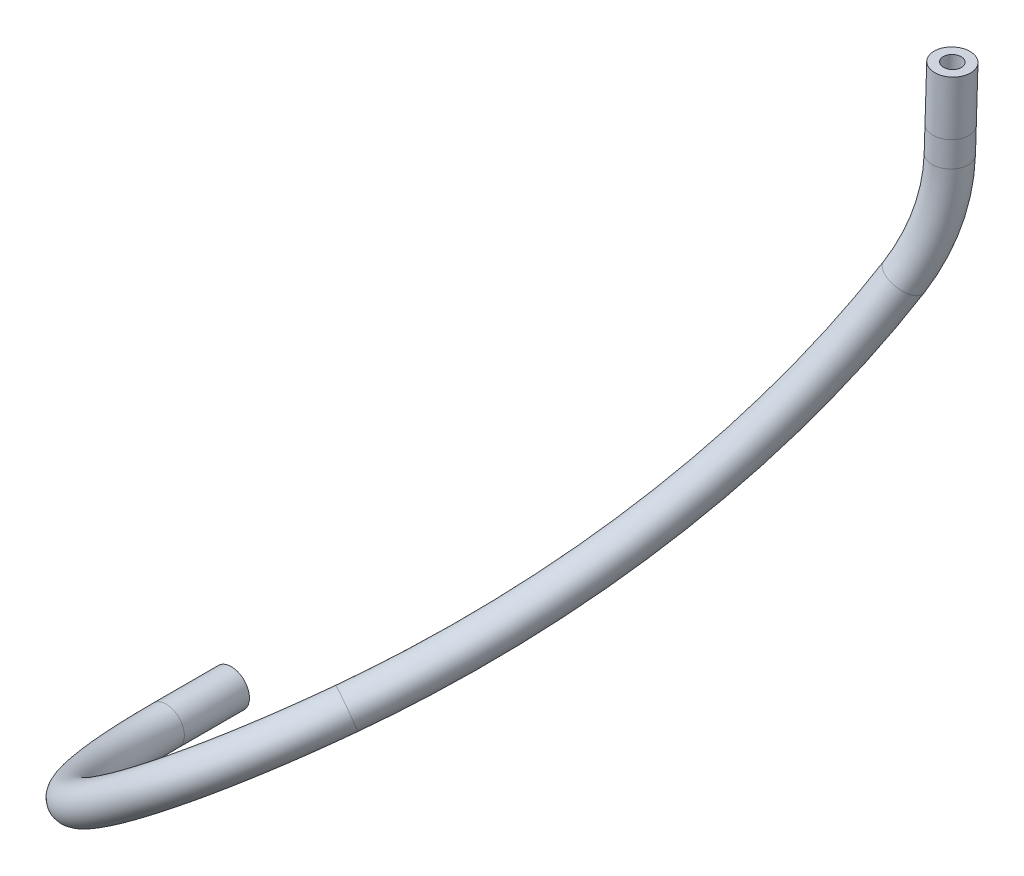
SolidWorks part; units mm, degrees
material "Silicon Rubber"
ref_plane "X-Y Datum" through (0, 0, 0) normal (0, 0, 1) x (1, 0, 0)
ref_plane "X-Z Datum" through (0, 0, 0) normal (0, 1, 0) x (1, 0, 0)
ref_plane "Y-Z Datum" through (0, 0, 0) normal (1, 0, 0) x (0, 0, -1)
sketch3d "3DSketch1"
  line L0 (44.0922, 18.6668, 9.7727) -> (44.0922, 18.6668, -12.9773)
  line L1 (44.0922, 18.6668, -12.9773) -> (44.0922, 18.6668, 9.7727) construction
  line L2 (233.3478, 252.6392, -75.3796) -> (233.125, 243.669, -75.3201)
  line L3 (233.8233, 271.7865, -75.5066) -> (233.3478, 252.6392, -75.3796)
  circle A0 centre (44.0922, 18.6668, 9.7727) radius 3.2466 construction
  circle A1 centre (233.8233, 271.7865, -75.5066) radius 9.525 construction
  arc A2 (44.0922, 18.6668, 9.7727) -> (145.7778, 93.8476, 48.368) centre (99.6708, 59.7586, 9.7727) ccw
  circle A3 centre (233.125, 243.669, -75.3201) radius 6.35 construction
  circle A4 centre (44.0922, 18.6668, 9.7727) radius 3.2466 construction
  arc A6 (40.1426, 18.718, -12.9773) -> (44.041, 14.7171, -12.9773) centre (44.0922, 18.6668, -12.9773) ccw construction
  arc A7 (233.125, 243.669, -75.3201) -> (224.9145, 206.1842, -67.4223) centre (183.0364, 245.2622, -22.6572) ccw
  arc A9 (44.041, 14.7171, -12.9773) -> (48.0419, 18.6156, -12.9773) centre (44.0922, 18.6668, -12.9773) ccw construction
  arc A10 (40.1426, 18.718, -12.9773) -> (44.041, 14.7171, -12.9773) centre (44.0922, 18.6668, -12.9773) ccw construction
  arc A11 (44.041, 14.7171, -12.9773) -> (48.0419, 18.6156, -12.9773) centre (44.0922, 18.6668, -12.9773) ccw construction
  arc A12 (48.0419, 18.6156, -12.9773) -> (40.1426, 18.718, -12.9773) centre (44.0922, 18.6668, -12.9773) ccw construction
  arc A13 (48.0419, 18.6156, -12.9773) -> (40.1426, 18.718, -12.9773) centre (44.0922, 18.6668, -12.9773) ccw construction
  arc A14 (145.7778, 93.8476, 48.368) -> (224.9145, 206.1842, -67.4223) centre (159.9581, 334.9183, 152.5086) ccw
  circle A15 centre (233.8233, 271.7865, -75.5066) radius 9.525 construction
  circle A16 centre (233.3478, 252.6392, -75.3796) radius 13.589 construction
  circle A17 centre (233.3478, 252.6392, -75.3796) radius 13.589 construction
  point P7 (58.579, 115.3372, 9.7727)
  point P8 (44.0922, 18.6668, 13.0192)
  point P13 (233.9137, 281.311, -75.5066)
  point P15 (233.524, 266.2271, -75.3796)
  point P17 (233.524, 266.2271, -75.3796)
  point P18 (44.0922, 18.6668, 13.0192)
  point P24 (44.0922, 18.6668, -9.0273)
  point P26 (44.0922, 18.6668, -9.0273)
  point P28 (44.0922, 18.6668, -9.0273)
  point P29 (44.0922, 18.6668, -9.0273)
  point P33 (44.0922, 18.6668, -9.0273)
  point P34 (44.0922, 18.6668, -9.0273)
  point P35 (233.9137, 281.311, -75.5066)
  point P37 (232.9673, 237.3211, -75.278)
  point P38 (130.3802, 246.2376, -72.7688)
  point P42 (394.5167, 276.3961, 256.0407)
  dimension "D1" = 72.6966
sweep "Sweep1" add path "3DSketch1" circular profile diameter 12.7 parameters "D3"=12.7
sweep "Cut-Sweep1" cut path "3DSketch1<3>" circular profile diameter 6.35 parameters "D3"=6.35
sketch3d "3DSketch1<3>" same geometry as "3DSketch1"
